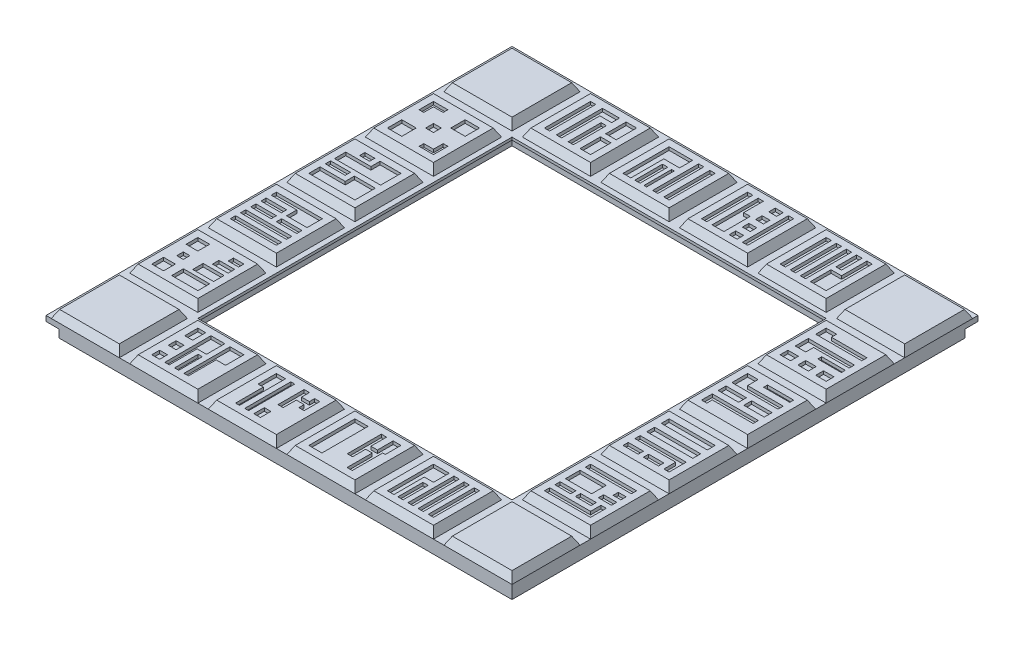
SolidWorks part; units mm, degrees
ref_plane "Front Plane" through (0, 0, 0) normal (0, 0, 1) x (1, 0, 0)
ref_plane "Top Plane" through (0, 0, 0) normal (0, 1, 0) x (1, 0, 0)
ref_plane "Right Plane" through (0, 0, 0) normal (1, 0, 0) x (0, 0, -1)
sketch "Sketch1" plane through (0, 0, 0) normal (0, 1, 0) x (1, 0, 0)
  line L1 (0, 0) -> (-180, 0)
  line L2 (0, 0) -> (0, 180)
  line L3 (0, 180) -> (-180, 180)
  line L4 (-180, 0) -> (-180, 180)
  dimension "D1" = 180
  dimension "D2" = 180
extrude "Boss-Extrude1" add sketch "Sketch1" along normal blind 5
sketch "Sketch2" plane through (0, 5, 0) normal (0, 1, 0) x (1, 0, 0)
  line L0 (-180, 180) -> (-180, 0) construction
  line L1 (-150, 150) -> (-30, 150)
  line L2 (-150, 150) -> (-150, 30)
  line L3 (-150, 30) -> (-30, 30)
  line L4 (-30, 150) -> (-30, 30)
  line L5 (0, 180) -> (-180, 180) construction
  dimension "D1" = 120
  dimension "D2" = 120
  dimension "D3" = 30
  dimension "D4" = 30
extrude "Cut-Extrude1" cut sketch "Sketch2" against normal through all
sketch "Sketch3" plane through (0, 5, 0) normal (0, 1, 0) x (1, 0, 0)
  line L0 (-180, 180) -> (-180, 0) construction
  line L1 (-178, 178) -> (-152, 178)
  line L2 (-178, 178) -> (-178, 152)
  line L3 (-178, 152) -> (-152, 152)
  line L4 (-152, 178) -> (-152, 152)
  line L5 (-148, 152) -> (-122, 152)
  line L6 (-148, 152) -> (-148, 178)
  line L7 (-148, 178) -> (-122, 178)
  line L8 (-122, 152) -> (-122, 178)
  line L9 (-118, 178) -> (-92, 178)
  line L10 (-118, 178) -> (-118, 152)
  line L11 (-118, 152) -> (-92, 152)
  line L12 (-92, 178) -> (-92, 152)
  line L13 (-88, 152) -> (-62, 152)
  line L14 (-88, 152) -> (-88, 178)
  line L15 (-88, 178) -> (-62, 178)
  line L16 (-62, 152) -> (-62, 178)
  line L17 (-58, 178) -> (-32, 178)
  line L18 (-58, 178) -> (-58, 152)
  line L19 (-58, 152) -> (-32, 152)
  line L20 (-32, 178) -> (-32, 152)
  line L21 (-28, 152) -> (-2, 152)
  line L22 (-28, 152) -> (-28, 178)
  line L23 (-28, 178) -> (-2, 178)
  line L24 (-2, 152) -> (-2, 178)
  line L25 (-28, 148) -> (-2, 148)
  line L26 (-28, 148) -> (-28, 122)
  line L27 (-28, 122) -> (-2, 122)
  line L28 (-2, 148) -> (-2, 122)
  line L29 (-2, 118) -> (-28, 118)
  line L30 (-2, 118) -> (-2, 92)
  line L31 (-2, 92) -> (-28, 92)
  line L32 (-28, 118) -> (-28, 92)
  line L33 (-28, 88) -> (-2, 88)
  line L34 (-28, 88) -> (-28, 62)
  line L35 (-28, 62) -> (-2, 62)
  line L36 (-2, 88) -> (-2, 62)
  line L37 (-28, 58) -> (-2, 58)
  line L38 (-28, 58) -> (-28, 32)
  line L39 (-28, 32) -> (-2, 32)
  line L40 (-2, 58) -> (-2, 32)
  line L41 (-28, 28) -> (-2, 28)
  line L42 (-28, 28) -> (-28, 2)
  line L43 (-28, 2) -> (-2, 2)
  line L44 (-2, 28) -> (-2, 2)
  line L45 (-32, 28) -> (-58, 28)
  line L46 (-32, 28) -> (-32, 2)
  line L47 (-32, 2) -> (-58, 2)
  line L48 (-58, 28) -> (-58, 2)
  line L49 (-62, 28) -> (-88, 28)
  line L50 (-62, 28) -> (-62, 2)
  line L51 (-62, 2) -> (-88, 2)
  line L52 (-88, 28) -> (-88, 2)
  line L53 (-92, 28) -> (-118, 28)
  line L54 (-92, 28) -> (-92, 2)
  line L55 (-92, 2) -> (-118, 2)
  line L56 (-118, 28) -> (-118, 2)
  line L57 (-122, 28) -> (-148, 28)
  line L58 (-122, 28) -> (-122, 2)
  line L59 (-122, 2) -> (-148, 2)
  line L60 (-148, 28) -> (-148, 2)
  line L61 (-152, 28) -> (-178, 28)
  line L62 (-152, 28) -> (-152, 2)
  line L63 (-152, 2) -> (-178, 2)
  line L64 (-178, 28) -> (-178, 2)
  line L65 (-178, 32) -> (-152, 32)
  line L66 (-178, 32) -> (-178, 58)
  line L67 (-178, 58) -> (-152, 58)
  line L68 (-152, 32) -> (-152, 58)
  line L69 (-178, 62) -> (-152, 62)
  line L70 (-178, 62) -> (-178, 88)
  line L71 (-178, 88) -> (-152, 88)
  line L72 (-152, 62) -> (-152, 88)
  line L73 (-178, 92) -> (-152, 92)
  line L74 (-178, 92) -> (-178, 118)
  line L75 (-178, 118) -> (-152, 118)
  line L76 (-152, 92) -> (-152, 118)
  line L77 (-178, 122) -> (-152, 122)
  line L78 (-178, 122) -> (-178, 148)
  line L79 (-178, 148) -> (-152, 148)
  line L80 (-152, 122) -> (-152, 148)
  line L81 (0, 180) -> (-180, 180) construction
  line L82 (-180, 0) -> (0, 0) construction
  line L83 (0, 0) -> (0, 180) construction
  dimension "D1" = 26
  dimension "D2" = 2
  dimension "D3" = 2
  dimension "D4" = 4
  dimension "D5" = 2
  dimension "D6" = 4
  dimension "D7" = 4
  dimension "D8" = 4
  dimension "D9" = 4
  dimension "D10" = 4
  dimension "D11" = 2
  dimension "D12" = 4
  dimension "D13" = 4
extrude "Boss-Extrude2" add sketch "Sketch3" along normal blind 3
chamfer "Chamfer1" distance 3 distance2 1.6 80 edges at (-15, 8, -178) (-2, 8, -165) (-15, 8, -152) (-28, 8, -165) (-105, 8, -2) (-118, 8, -15) (-105, 8, -28) (-92, 8, -15) (-135, 8, -2) (-148, 8, -15) (-135, 8, -28) (-122, 8, -15) (-165, 8, -2) (-178, 8, -15) (-165, 8, -28) (-152, 8, -15) (-165, 8, -58) (-152, 8, -45) (-165, 8, -32) (-178, 8, -45) (-165, 8, -88) (-152, 8, -75) (-165, 8, -62) (-178, 8, -75) (-165, 8, -118) (-152, 8, -105) (-165, 8, -92) (-178, 8, -105) (-15, 8, -58) (-2, 8, -45) (-15, 8, -32) (-28, 8, -45) (-75, 8, -2) (-88, 8, -15) (-75, 8, -28) (-62, 8, -15) (-45, 8, -2) (-58, 8, -15) (-45, 8, -28) (-32, 8, -15) (-15, 8, -28) (-2, 8, -15) (-15, 8, -2) (-28, 8, -15) (-15, 8, -88) (-2, 8, -75) (-15, 8, -62) (-28, 8, -75) (-15, 8, -92) (-28, 8, -105) (-15, 8, -118) (-2, 8, -105) (-15, 8, -148) (-2, 8, -135) (-15, 8, -122) (-28, 8, -135) (-75, 8, -178) (-62, 8, -165) (-75, 8, -152) (-88, 8, -165) (-105, 8, -178) (-92, 8, -165) (-105, 8, -152) (-118, 8, -165) (-135, 8, -178) (-122, 8, -165) (-135, 8, -152) (-148, 8, -165) (-165, 8, -148) (-152, 8, -135) (-165, 8, -122) (-178, 8, -135) (-165, 8, -178) (-152, 8, -165) (-165, 8, -152) (-178, 8, -165) (-45, 8, -178) (-32, 8, -165) (-45, 8, -152) (-58, 8, -165)
sketch "Sketch4" plane through (0, 8, 0) normal (0, 1, 0) x (1, 0, 0)
  line L0 (-123.6, 176.4) -> (-146.4, 176.4) construction
  line L1 (-143.8, 173.8) -> (-141.8, 173.8)
  line L2 (-143.8, 173.8) -> (-143.8, 156.2)
  line L3 (-143.8, 156.2) -> (-141.8, 156.2)
  line L4 (-141.8, 173.8) -> (-141.8, 156.2)
  line L5 (-139.25, 156.2) -> (-137.25, 156.2)
  line L6 (-139.25, 156.2) -> (-139.25, 173.8)
  line L7 (-139.25, 173.8) -> (-137.25, 173.8)
  line L8 (-137.25, 156.2) -> (-137.25, 173.8)
  line L9 (-137.25, 173.8) -> (-132.75, 173.8)
  line L10 (-146.4, 153.6) -> (-123.6, 153.6) construction
  line L11 (-137.25, 170.8) -> (-132.75, 170.8)
  line L12 (-132.75, 173.8) -> (-132.75, 170.8)
  line L13 (-132.75, 168.8) -> (-134.75, 168.8)
  line L14 (-132.75, 168.8) -> (-132.75, 156.2)
  line L15 (-132.75, 156.2) -> (-134.75, 156.2)
  line L16 (-134.75, 168.8) -> (-134.75, 156.2)
  line L17 (-130.2, 156.2) -> (-126.2, 156.2)
  line L18 (-130.2, 156.2) -> (-130.2, 164)
  line L19 (-130.2, 164) -> (-126.2, 164)
  line L20 (-126.2, 156.2) -> (-126.2, 164)
  line L21 (-130.2, 166) -> (-126.2, 166)
  line L22 (-130.2, 166) -> (-130.2, 173.8)
  line L23 (-130.2, 173.8) -> (-126.2, 173.8)
  line L24 (-126.2, 166) -> (-126.2, 173.8)
  line L25 (-113.8, 156.2) -> (-110.8, 156.2)
  line L26 (-113.8, 156.2) -> (-113.8, 173.8)
  line L27 (-113.8, 173.8) -> (-110.8, 173.8)
  line L28 (-110.8, 156.2) -> (-110.8, 173.8)
  line L29 (-110.8, 168.8) -> (-104.8, 168.8)
  line L30 (-146.4, 176.4) -> (-146.4, 153.6) construction
  line L31 (-110.8, 173.8) -> (-104.8, 173.8)
  line L32 (-104.8, 168.8) -> (-104.8, 173.8)
  line L33 (-109.3, 166.8) -> (-107.3, 166.8)
  line L34 (-109.3, 166.8) -> (-109.3, 156.2)
  line L35 (-109.3, 156.2) -> (-107.3, 156.2)
  line L36 (-107.3, 166.8) -> (-107.3, 156.2)
  line L37 (-105.8, 156.2) -> (-104.8, 156.2)
  line L38 (-105.8, 156.2) -> (-105.8, 166.8)
  line L39 (-105.8, 166.8) -> (-104.8, 166.8)
  line L40 (-104.8, 156.2) -> (-104.8, 166.8)
  line L41 (-102.5, 173.8) -> (-100.5, 173.8)
  line L42 (-102.5, 173.8) -> (-102.5, 156.2)
  line L43 (-102.5, 156.2) -> (-100.5, 156.2)
  line L44 (-100.5, 173.8) -> (-100.5, 156.2)
  line L45 (-98.2, 156.2) -> (-96.2, 156.2)
  line L46 (-98.2, 156.2) -> (-98.2, 173.8)
  line L47 (-98.2, 173.8) -> (-96.2, 173.8)
  line L48 (-96.2, 156.2) -> (-96.2, 173.8)
  line L49 (-83.8, 173.8) -> (-81.8, 173.8)
  line L50 (-83.8, 173.8) -> (-83.8, 156.2)
  line L51 (-83.8, 156.2) -> (-81.8, 156.2)
  line L52 (-81.8, 173.8) -> (-81.8, 156.2)
  line L53 (-79.7667, 156.2) -> (-77.7667, 156.2)
  line L54 (-79.7667, 156.2) -> (-79.7667, 173.8)
  line L55 (-79.7667, 173.8) -> (-77.7667, 173.8)
  line L56 (-77.7667, 156.2) -> (-77.7667, 173.8)
  line L57 (-77.7667, 166.2667) -> (-75.2667, 166.2667)
  line L58 (-123.6, 153.6) -> (-123.6, 176.4) construction
  line L59 (-77.7667, 156.2) -> (-75.2667, 156.2)
  line L60 (-75.2667, 166.2667) -> (-75.2667, 156.2)
  line L61 (-73.2333, 156.2) -> (-70.2333, 156.2)
  line L62 (-73.2333, 156.2) -> (-73.2333, 158.7)
  line L63 (-73.2333, 158.7) -> (-70.2333, 158.7)
  line L64 (-70.2333, 156.2) -> (-70.2333, 158.7)
  line L65 (-73.2333, 161.2333) -> (-70.2333, 161.2333)
  line L66 (-73.2333, 161.2333) -> (-73.2333, 163.7333)
  line L67 (-73.2333, 163.7333) -> (-70.2333, 163.7333)
  line L68 (-70.2333, 161.2333) -> (-70.2333, 163.7333)
  line L69 (-73.2333, 166.2667) -> (-70.2333, 166.2667)
  line L70 (-73.2333, 166.2667) -> (-73.2333, 168.7667)
  line L71 (-73.2333, 168.7667) -> (-70.2333, 168.7667)
  line L72 (-70.2333, 166.2667) -> (-70.2333, 168.7667)
  line L73 (-73.2333, 171.3) -> (-70.2333, 171.3)
  line L74 (-73.2333, 171.3) -> (-73.2333, 173.8)
  line L75 (-73.2333, 173.8) -> (-70.2333, 173.8)
  line L76 (-70.2333, 171.3) -> (-70.2333, 173.8)
  line L77 (-68.2, 173.8) -> (-66.2, 173.8)
  line L78 (-68.2, 173.8) -> (-68.2, 156.2)
  line L79 (-68.2, 156.2) -> (-66.2, 156.2)
  line L80 (-66.2, 173.8) -> (-66.2, 156.2)
  line L81 (-53.8, 173.8) -> (-51.8, 173.8)
  line L82 (-53.8, 173.8) -> (-53.8, 156.2)
  line L83 (-53.8, 156.2) -> (-51.8, 156.2)
  line L84 (-51.8, 173.8) -> (-51.8, 156.2)
  line L85 (-49.9333, 156.2) -> (-47.9333, 156.2)
  line L86 (-49.9333, 156.2) -> (-49.9333, 173.8)
  line L87 (-49.9333, 173.8) -> (-47.9333, 173.8)
  line L88 (-47.9333, 156.2) -> (-47.9333, 173.8)
  line L89 (-46.0667, 173.8) -> (-44.0667, 173.8)
  line L90 (-46.0667, 173.8) -> (-46.0667, 156.2)
  line L91 (-46.0667, 156.2) -> (-44.0667, 156.2)
  line L92 (-44.0667, 173.8) -> (-44.0667, 156.2)
  line L93 (-42.2, 173.8) -> (-40.0667, 173.8)
  line L94 (-42.2, 173.8) -> (-42.2, 165.9333)
  line L95 (-42.2, 165.9333) -> (-40.0667, 165.9333)
  line L96 (-40.0667, 173.8) -> (-40.0667, 165.9333)
  line L97 (-38.2, 173.8) -> (-36.2, 173.8)
  line L98 (-38.2, 173.8) -> (-38.2, 156.2)
  line L99 (-38.2, 156.2) -> (-36.2, 156.2)
  line L100 (-36.2, 173.8) -> (-36.2, 156.2)
  line L101 (-42.2, 156.2) -> (-38.2, 156.2)
  line L102 (-42.2, 156.2) -> (-42.2, 164.0667)
  line L103 (-42.2, 164.0667) -> (-38.2, 164.0667)
  line L104 (-93.6, 153.6) -> (-93.6, 176.4) construction
  line L105 (-116.4, 176.4) -> (-116.4, 153.6) construction
  line L106 (-63.6, 153.6) -> (-63.6, 176.4) construction
  line L107 (-86.4, 176.4) -> (-86.4, 153.6) construction
  line L108 (-56.4, 176.4) -> (-56.4, 153.6) construction
  line L109 (-33.6, 153.6) -> (-33.6, 176.4) construction
  line L110 (-70.2333, 171.3) -> (-70.2333, 168.7667) construction
  line L111 (-70.2333, 166.2667) -> (-70.2333, 163.7333) construction
  line L112 (-70.2333, 161.2333) -> (-70.2333, 158.7) construction
  line L113 (-141.8, 156.2) -> (-139.25, 156.2) construction
  line L114 (-132.75, 156.2) -> (-130.2, 156.2) construction
  line L115 (-104.8, 156.2) -> (-102.5, 156.2) construction
  line L116 (-100.5, 156.2) -> (-98.2, 156.2) construction
  line L117 (-51.8, 156.2) -> (-49.9333, 156.2) construction
  line L118 (-47.9333, 156.2) -> (-46.0667, 156.2) construction
  line L119 (-44.0667, 156.2) -> (-42.2, 156.2) construction
  line L120 (-42.2, 164.0667) -> (-42.2, 165.9333) construction
  line L121 (-40.0667, 173.8) -> (-38.2, 173.8) construction
  line L122 (-81.8, 156.2) -> (-79.7667, 156.2) construction
  line L123 (-75.2667, 156.2) -> (-73.2333, 156.2) construction
  line L124 (-70.2333, 156.2) -> (-68.2, 156.2) construction
  point P120 (-127.7927, 145.733)
  dimension "D1" = 2.6
  dimension "D2" = 2.6
  dimension "D3" = 2.6
  dimension "D4" = 2.6
  dimension "D5" = 2.6
  dimension "D6" = 2
  dimension "D7" = 2
  dimension "D8" = 2
  dimension "D9" = 1
  dimension "D10" = 2
  dimension "D11" = 2
  dimension "D12" = 2.6
  dimension "D13" = 2.6
  dimension "D14" = 2.6
  dimension "D15" = 2.6
  dimension "D16" = 2
  dimension "D17" = 2
  dimension "D18" = 2.5
  dimension "D19" = 2
  dimension "D21" = 3
  dimension "D23" = 2.6
  dimension "D24" = 2.6
  dimension "D25" = 2
  dimension "D26" = 2.5
  dimension "D27" = 2
  dimension "D28" = 3
  dimension "D29" = 2
  dimension "D30" = 2
  dimension "D31" = 4
  dimension "D32" = 4
  dimension "D33" = 3
  dimension "D34" = 6
  dimension "D35" = 1.5
  dimension "D36" = 5
  dimension "D37" = 2
  dimension "D38" = 2
  dimension "D39" = 2
  dimension "D40" = 2.5
  dimension "D41" = 2
  dimension "D42" = 2
  dimension "D43" = 4
extrude "Motifs_Ligne_1" cut sketch "Sketch4" against normal blind 1.2 contours L13 L16 L15 L14 | L12 L9 L8 L11 | L17 L20 L19 L18 | L21 L24 L23 L22 | L5 L8 L7 L6 | L25 L28 L27 L26 | L29 L32 L31 L28 | L36 L33 L34 L35 | L37 L40 L39 L38 | L44 L41 L42 L43 | L45 L48 L47 L46 | L103 L102 L101 L98 | L100 L97 L98 L99 | L96 L93 L94 L95 | L92 L89 L90 L91 | L85 L88 L87 L86 | L84 L81 L82 L83 | L73 L76 L75 L74 | L53 L56 L55 L54 | L60 L57 L56 L59 | L52 L49 L50 L51 | L65 L68 L67 L66 | L61 L64 L63 L62 | L69 L72 L71 L70 | L80 L77 L78 L79 | L2 L3 L4 L1
sketch "Sketch5" plane through (0, 0, 0) normal (0, -1, 0) x (1, 0, 0)
  line L0 (0, -175) -> (0, -180)
  line L1 (-180, -180) -> (-180, 0)
  line L2 (-180, 0) -> (-175, 0)
  line L4 (-175, -175) -> (0, -175)
  line L5 (0, -180) -> (-180, -180)
  line L6 (-175, 0) -> (-175, -175)
  line L7 (-180, 0) -> (0, 0) construction
  dimension "D1" = 5
  dimension "D2" = 5
  dimension "D3" = 0
  dimension "D4" = 0
extrude "Cut-Extrude3" cut sketch "Sketch5" against normal blind 3
sketch "Sketch6" plane through (0, 0, 0) normal (0, -1, 0) x (1, 0, 0)
  line L0 (0, 0) -> (0, -194.7494)
  line L1 (0, -194.7494) -> (-2, -194.7494)
  line L2 (-2, -194.7494) -> (-2, -2)
  line L3 (-2, -2) -> (-190.0347, -2)
  line L4 (-190.0347, -2) -> (-190.0347, 0)
  line L5 (-190.0347, 0) -> (0, 0)
  dimension "D1" = 2
  dimension "D2" = 2
extrude "Cut-Extrude4" cut sketch "Sketch6" against normal through all
sketch "Sketch7" plane through (0, 8, 0) normal (0, 1, 0) x (1, 0, 0)
  line L0 (-173.8, 146.4) -> (-173.8, 33.6) construction
  line L1 (-153.6, 146.4) -> (-176.4, 146.4) construction
  line L2 (-176.4, 33.6) -> (-153.6, 33.6) construction
  line L3 (-156.2, 146.4) -> (-156.2, 33.6) construction
  line L4 (-176.4, 36.2) -> (-153.6, 36.2) construction
  line L5 (-176.4, 56.4) -> (-176.4, 33.6) construction
  line L6 (-153.6, 33.6) -> (-153.6, 56.4) construction
  line L7 (-176.4, 143.8) -> (-153.6, 143.8) construction
  line L8 (-176.4, 146.4) -> (-176.4, 123.6) construction
  line L9 (-153.6, 123.6) -> (-153.6, 146.4) construction
  line L10 (-176.4, 126.2) -> (-153.6, 126.2) construction
  line L11 (-176.4, 96.2) -> (-153.6, 96.2) construction
  line L12 (-176.4, 116.4) -> (-176.4, 93.6) construction
  line L13 (-153.6, 93.6) -> (-153.6, 116.4) construction
  line L14 (-176.4, 113.8) -> (-153.6, 113.8) construction
  line L15 (-176.4, 83.8) -> (-153.6, 83.8) construction
  line L16 (-176.4, 86.4) -> (-176.4, 63.6) construction
  line L17 (-153.6, 63.6) -> (-153.6, 86.4) construction
  line L18 (-153.6, 66.2) -> (-176.4, 66.2) construction
  line L19 (-176.4, 53.8) -> (-153.6, 53.8) construction
  line L20 (-176.4, 123.6) -> (-153.6, 123.6) construction
  line L21 (-153.6, 116.4) -> (-176.4, 116.4) construction
  line L22 (-176.4, 93.6) -> (-153.6, 93.6) construction
  line L23 (-153.6, 86.4) -> (-176.4, 86.4) construction
  line L24 (-176.4, 63.6) -> (-153.6, 63.6) construction
  line L25 (-153.6, 56.4) -> (-176.4, 56.4) construction
  line L26 (-173.8, 138.3) -> (-172, 138.3)
  line L27 (-173.8, 126.2) -> (-168.3, 126.2)
  line L28 (-173.8, 126.2) -> (-173.8, 131.7)
  line L29 (-173.8, 131.7) -> (-168.3, 131.7)
  line L30 (-168.3, 126.2) -> (-168.3, 131.7)
  line L31 (-166.5, 133.5) -> (-163.5, 133.5)
  line L32 (-166.5, 133.5) -> (-166.5, 136.5)
  line L33 (-166.5, 136.5) -> (-163.5, 136.5)
  line L34 (-163.5, 133.5) -> (-163.5, 136.5)
  line L35 (-156.2, 143.8) -> (-161.7, 143.8)
  line L36 (-156.2, 143.8) -> (-156.2, 138.3)
  line L37 (-156.2, 138.3) -> (-161.7, 138.3)
  line L38 (-161.7, 143.8) -> (-161.7, 138.3)
  line L39 (-172, 138.3) -> (-172, 142)
  line L40 (-172, 142) -> (-168.3, 142)
  line L41 (-168.3, 142) -> (-168.3, 143.8)
  line L42 (-168.3, 143.8) -> (-173.8, 143.8)
  line L43 (-173.8, 143.8) -> (-173.8, 138.3)
  line L44 (-161.7, 126.2) -> (-156.2, 126.2)
  line L45 (-156.2, 126.2) -> (-156.2, 131.7)
  line L46 (-156.2, 131.7) -> (-158, 131.7)
  line L47 (-158, 131.7) -> (-158, 128)
  line L48 (-158, 128) -> (-161.7, 128)
  line L49 (-161.7, 126.2) -> (-161.7, 128)
  line L50 (-173.8, 131.7) -> (-173.8, 138.3) construction
  line L51 (-168.3, 143.8) -> (-161.7, 143.8) construction
  line L52 (-168.3, 126.2) -> (-161.7, 126.2) construction
  line L53 (-156.2, 131.7) -> (-156.2, 138.3) construction
  line L54 (-172, 138.3) -> (-172, 131.7) construction
  line L55 (-166.5, 133.5) -> (-173.8, 133.5) construction
  line L56 (-166.5, 133.5) -> (-166.5, 126.2) construction
  line L57 (-163.5, 136.5) -> (-163.5, 143.8) construction
  line L58 (-163.5, 136.5) -> (-156.2, 136.5) construction
  line L59 (-173.8, 106) -> (-156.2, 106)
  line L60 (-156.2, 106) -> (-156.2, 113.8)
  line L61 (-156.2, 113.8) -> (-164.2, 113.8)
  line L62 (-164.2, 113.8) -> (-164.2, 110.3)
  line L63 (-164.2, 110.3) -> (-173.8, 110.3)
  line L64 (-173.8, 110.3) -> (-173.8, 106)
  line L65 (-173.8, 96.2) -> (-173.8, 100.5)
  line L66 (-173.8, 100.5) -> (-164.2, 100.5)
  line L67 (-164.2, 100.5) -> (-164.2, 104)
  line L68 (-164.2, 104) -> (-156.2, 104)
  line L69 (-156.2, 104) -> (-156.2, 96.2)
  line L70 (-156.2, 96.2) -> (-173.8, 96.2)
  line L71 (-173.8, 83.8) -> (-156.2, 83.8)
  line L72 (-173.8, 104.5) -> (-166.2, 104.5)
  line L73 (-173.8, 104.5) -> (-173.8, 102.5)
  line L74 (-173.8, 102.5) -> (-166.2, 102.5)
  line L75 (-166.2, 104.5) -> (-166.2, 102.5)
  line L76 (-170, 113.8) -> (-166.2, 113.8)
  line L77 (-170, 113.8) -> (-170, 111.8)
  line L78 (-170, 111.8) -> (-166.2, 111.8)
  line L79 (-166.2, 113.8) -> (-166.2, 111.8)
  line L80 (-173.8, 66.2) -> (-156.2, 66.2)
  line L81 (-173.8, 66.2) -> (-173.8, 68.2)
  line L82 (-173.8, 68.2) -> (-156.2, 68.2)
  line L83 (-156.2, 66.2) -> (-156.2, 68.2)
  line L84 (-156.2, 70.1) -> (-173.8, 70.1)
  line L85 (-156.2, 70.1) -> (-156.2, 72.1)
  line L86 (-156.2, 72.1) -> (-173.8, 72.1)
  line L87 (-173.8, 70.1) -> (-173.8, 72.1)
  line L88 (-173.8, 74) -> (-166, 74)
  line L89 (-173.8, 74) -> (-173.8, 76)
  line L90 (-173.8, 76) -> (-166, 76)
  line L91 (-166, 74) -> (-166, 76)
  line L92 (-164, 76) -> (-156.2, 76)
  line L93 (-164, 76) -> (-164, 74)
  line L94 (-164, 74) -> (-156.2, 74)
  line L95 (-156.2, 76) -> (-156.2, 74)
  line L96 (-173.8, 77.9) -> (-166, 77.9)
  line L97 (-173.8, 77.9) -> (-173.8, 79.9)
  line L98 (-173.8, 79.9) -> (-166, 79.9)
  line L99 (-166, 77.9) -> (-166, 79.9)
  line L100 (-156.2, 83.8) -> (-156.2, 77.9)
  line L101 (-156.2, 77.9) -> (-164, 77.9)
  line L102 (-164, 77.9) -> (-164, 81.8)
  line L103 (-164, 81.8) -> (-173.8, 81.8)
  line L104 (-173.8, 81.8) -> (-173.8, 83.8)
  line L105 (-173.8, 68.2) -> (-173.8, 70.1) construction
  line L106 (-173.8, 72.1) -> (-173.8, 74) construction
  line L107 (-166, 79.9) -> (-166, 81.8) construction
  line L108 (-166, 77.9) -> (-166, 76) construction
  line L109 (-166, 74) -> (-166, 72.1) construction
  line L110 (-166, 70.1) -> (-166, 68.2) construction
  line L111 (-159.5704, 40.7) -> (-159.5704, 42.2333) construction
  line L112 (-173.8, 53.8) -> (-169.3, 53.8)
  line L113 (-173.8, 53.8) -> (-173.8, 49.3)
  line L114 (-173.8, 49.3) -> (-169.3, 49.3)
  line L115 (-169.3, 53.8) -> (-169.3, 49.3)
  line L116 (-173.8, 36.2) -> (-169.3, 36.2)
  line L117 (-173.8, 36.2) -> (-173.8, 40.7)
  line L118 (-173.8, 40.7) -> (-169.3, 40.7)
  line L119 (-169.3, 36.2) -> (-169.3, 40.7)
  line L120 (-169.3, 43.75) -> (-171.8, 43.75)
  line L121 (-169.3, 43.75) -> (-169.3, 46.25)
  line L122 (-169.3, 46.25) -> (-171.8, 46.25)
  line L123 (-171.8, 43.75) -> (-171.8, 46.25)
  line L124 (-156.2, 53.8) -> (-160.2, 53.8)
  line L125 (-156.2, 53.8) -> (-156.2, 51.8)
  line L126 (-156.2, 51.8) -> (-160.2, 51.8)
  line L127 (-160.2, 53.8) -> (-160.2, 51.8)
  line L128 (-156.2, 50.2667) -> (-162.2, 50.2667)
  line L129 (-156.2, 50.2667) -> (-156.2, 47.7667)
  line L130 (-156.2, 47.7667) -> (-162.2, 47.7667)
  line L131 (-162.2, 50.2667) -> (-162.2, 47.7667)
  line L132 (-156.2, 46.2333) -> (-164.2, 46.2333)
  line L133 (-156.2, 46.2333) -> (-156.2, 42.2333)
  line L134 (-156.2, 42.2333) -> (-164.2, 42.2333)
  line L135 (-164.2, 46.2333) -> (-164.2, 42.2333)
  line L136 (-156.2, 40.7) -> (-166.2, 40.7)
  line L137 (-156.2, 40.7) -> (-156.2, 36.2)
  line L138 (-156.2, 36.2) -> (-166.2, 36.2)
  line L139 (-166.2, 40.7) -> (-166.2, 36.2)
  line L140 (-159.5704, 46.2333) -> (-159.5704, 47.7667) construction
  line L141 (-159.5704, 50.2667) -> (-159.5704, 51.8) construction
  line L142 (-169.3, 46.25) -> (-169.3, 49.3) construction
  line L143 (-169.3, 43.75) -> (-169.3, 40.7) construction
  dimension "D1" = 2.6
  dimension "D2" = 2.6
  dimension "D3" = 2.6
  dimension "D4" = 2.6
  dimension "D5" = 2.6
  dimension "D6" = 2.6
  dimension "D7" = 2.6
  dimension "D8" = 2.6
  dimension "D9" = 2.6
  dimension "D10" = 2.6
  dimension "D11" = 1.8
  dimension "D12" = 5.5
  dimension "D13" = 1.5
  dimension "D14" = 3
  dimension "D15" = 2
  dimension "D16" = 2
  dimension "D17" = 2
  dimension "D18" = 8
  dimension "D19" = 2
  dimension "D20" = 3.8
  dimension "D21" = 2
  dimension "D22" = 2
  dimension "D23" = 2
  dimension "D24" = 2.5
  dimension "D25" = 4
  dimension "D26" = 4.5
  dimension "D27" = 10
  dimension "D28" = 8
  dimension "D29" = 6
  dimension "D30" = 4
  dimension "D31" = 2.5
  dimension "D32" = 4.5
extrude "Cut-Extrude5" cut sketch "Sketch7" against normal blind 1.2
sketch "Sketch8" plane through (0, 8, 0) normal (0, 1, 0) x (1, 0, 0)
  line L0 (-23.8, 38.2) -> (-23.8, 36.2)
  line L1 (-15.2, 133.5) -> (-6.2, 133.5)
  line L2 (-15.2, 133.5) -> (-15.2, 132)
  line L3 (-15.2, 132) -> (-6.2, 132)
  line L4 (-6.2, 133.5) -> (-6.2, 132)
  line L5 (-23.8, 129.2) -> (-19.8, 129.2)
  line L6 (-23.8, 129.2) -> (-23.8, 126.2)
  line L7 (-23.8, 126.2) -> (-19.8, 126.2)
  line L8 (-19.8, 129.2) -> (-19.8, 126.2)
  line L9 (-17, 129.2) -> (-13, 129.2)
  line L10 (-17, 129.2) -> (-17, 126.2)
  line L11 (-17, 126.2) -> (-13, 126.2)
  line L12 (-13, 129.2) -> (-13, 126.2)
  line L13 (-10.2, 129.2) -> (-6.2, 129.2)
  line L14 (-10.2, 129.2) -> (-10.2, 126.2)
  line L15 (-10.2, 126.2) -> (-6.2, 126.2)
  line L16 (-6.2, 129.2) -> (-6.2, 126.2)
  line L17 (-16.2, 113.8) -> (-6.2, 113.8)
  line L18 (-16.2, 113.8) -> (-16.2, 112.3)
  line L19 (-16.2, 112.3) -> (-6.2, 112.3)
  line L20 (-6.2, 113.8) -> (-6.2, 112.3)
  line L21 (-23.8, 105.5524) -> (-16, 105.5524)
  line L22 (-23.8, 105.5524) -> (-23.8, 102.5524)
  line L23 (-23.8, 102.5524) -> (-16, 102.5524)
  line L24 (-16, 105.5524) -> (-16, 102.5524)
  line L25 (-14, 105.5524) -> (-6.2, 105.5524)
  line L26 (-14, 105.5524) -> (-14, 102.5524)
  line L27 (-14, 102.5524) -> (-6.2, 102.5524)
  line L28 (-6.2, 105.5524) -> (-6.2, 102.5524)
  line L29 (-23.8, 83.8) -> (-6.2, 83.8)
  line L30 (-23.8, 83.8) -> (-23.8, 80.8)
  line L31 (-23.8, 80.8) -> (-6.2, 80.8)
  line L32 (-6.2, 83.8) -> (-6.2, 80.8)
  line L33 (-6.2, 78.2667) -> (-23.8, 78.2667)
  line L34 (-6.2, 78.2667) -> (-6.2, 75.2667)
  line L35 (-6.2, 75.2667) -> (-23.8, 75.2667)
  line L36 (-23.8, 78.2667) -> (-23.8, 75.2667)
  line L37 (-23.8, 68.2) -> (-18, 68.2)
  line L38 (-23.8, 68.2) -> (-23.8, 66.2)
  line L39 (-23.8, 66.2) -> (-18, 66.2)
  line L40 (-18, 68.2) -> (-18, 66.2)
  line L41 (-16, 68.2) -> (-10.2, 68.2)
  line L42 (-16, 68.2) -> (-16, 66.2)
  line L43 (-16, 66.2) -> (-10.2, 66.2)
  line L44 (-10.2, 68.2) -> (-10.2, 66.2)
  line L45 (-23.8, 53.8) -> (-6.2, 53.8)
  line L46 (-23.8, 53.8) -> (-23.8, 51.8)
  line L47 (-23.8, 51.8) -> (-6.2, 51.8)
  line L48 (-6.2, 53.8) -> (-6.2, 51.8)
  line L49 (-23.8, 49.8) -> (-13.8, 49.8)
  line L50 (-23.8, 49.8) -> (-23.8, 44.2)
  line L51 (-23.8, 44.2) -> (-13.8, 44.2)
  line L52 (-13.8, 49.8) -> (-13.8, 44.2)
  line L53 (-9.2, 49.8) -> (-6.2, 49.8)
  line L54 (-9.2, 49.8) -> (-9.2, 47.8)
  line L55 (-9.2, 47.8) -> (-6.2, 47.8)
  line L56 (-6.2, 49.8) -> (-6.2, 47.8)
  line L57 (-11.2, 46.2) -> (-6.2, 46.2)
  line L58 (-11.2, 46.2) -> (-11.2, 44.2)
  line L59 (-11.2, 44.2) -> (-6.2, 44.2)
  line L60 (-6.2, 46.2) -> (-6.2, 44.2)
  line L61 (-23.8, 42.2) -> (-17.8, 42.2)
  line L62 (-23.8, 42.2) -> (-23.8, 40.2)
  line L63 (-23.8, 40.2) -> (-17.8, 40.2)
  line L64 (-17.8, 42.2) -> (-17.8, 40.2)
  line L65 (-16, 42.2) -> (-10, 42.2)
  line L66 (-16, 42.2) -> (-16, 40.2)
  line L67 (-16, 40.2) -> (-10, 40.2)
  line L68 (-10, 42.2) -> (-10, 40.2)
  line L69 (-23.8, 36.2) -> (-6.2, 36.2)
  line L70 (-6.2, 36.2) -> (-6.2, 42.2)
  line L71 (-6.2, 42.2) -> (-8.2, 42.2)
  line L72 (-8.2, 42.2) -> (-8.2, 38.2)
  line L73 (-8.2, 38.2) -> (-23.8, 38.2)
  line L74 (-23.8, 70.7333) -> (-23.8, 72.7333)
  line L75 (-23.8, 72.7333) -> (-6.2, 72.7333)
  line L76 (-6.2, 72.7333) -> (-6.2, 66.2)
  line L77 (-6.2, 66.2) -> (-8.2, 66.2)
  line L78 (-8.2, 66.2) -> (-8.2, 70.7333)
  line L79 (-8.2, 70.7333) -> (-23.8, 70.7333)
  line L80 (-23.8, 96.2) -> (-23.8, 100.3049)
  line L81 (-23.8, 100.3049) -> (-6.2, 100.3049)
  line L82 (-6.2, 100.3049) -> (-6.2, 98.3049)
  line L83 (-6.2, 98.3049) -> (-21.8, 98.3049)
  line L84 (-21.8, 98.3049) -> (-21.8, 96.2)
  line L85 (-21.8, 96.2) -> (-23.8, 96.2)
  line L86 (-23.8, 113.8) -> (-23.8, 107.8)
  line L87 (-23.8, 107.8) -> (-6.2, 107.8)
  line L88 (-6.2, 107.8) -> (-6.2, 109.8)
  line L89 (-6.2, 109.8) -> (-19.8, 109.8)
  line L90 (-19.8, 109.8) -> (-19.8, 113.8)
  line L91 (-19.8, 113.8) -> (-23.8, 113.8)
  line L92 (-23.8, 132) -> (-19.8, 132)
  line L93 (-19.8, 132) -> (-19.8, 135)
  line L94 (-19.8, 135) -> (-6.2, 135)
  line L95 (-6.2, 135) -> (-6.2, 137)
  line L96 (-6.2, 137) -> (-23.8, 137)
  line L97 (-23.8, 137) -> (-23.8, 132)
  line L98 (-23.8, 143.8) -> (-23.8, 139.8)
  line L99 (-23.8, 139.8) -> (-6.2, 139.8)
  line L100 (-6.2, 139.8) -> (-6.2, 141.8)
  line L101 (-6.2, 141.8) -> (-19.8, 141.8)
  line L102 (-19.8, 141.8) -> (-19.8, 143.8)
  line L103 (-19.8, 143.8) -> (-23.8, 143.8)
  line L104 (-3.6, 33.6) -> (-3.6, 56.4) construction
  line L105 (-26.4, 146.4) -> (-26.4, 123.6) construction
  line L106 (-3.6, 146.4) -> (-26.4, 146.4) construction
  line L107 (-26.4, 123.6) -> (-3.6, 123.6) construction
  line L108 (-3.6, 116.4) -> (-26.4, 116.4) construction
  line L109 (-26.4, 93.6) -> (-3.6, 93.6) construction
  line L110 (-3.6, 86.4) -> (-26.4, 86.4) construction
  line L111 (-26.4, 63.6) -> (-3.6, 63.6) construction
  line L112 (-3.6, 56.4) -> (-26.4, 56.4) construction
  line L113 (-26.4, 33.6) -> (-3.6, 33.6) construction
  line L114 (-23.8, 68.2) -> (-23.8, 70.7333) construction
  line L115 (-23.8, 72.7333) -> (-23.8, 75.2667) construction
  line L116 (-23.8, 78.2667) -> (-23.8, 80.8) construction
  line L117 (-23.8, 38.2) -> (-23.8, 40.2) construction
  line L118 (-23.8, 42.2) -> (-23.8, 44.2) construction
  line L119 (-23.8, 49.8) -> (-23.8, 51.8) construction
  line L120 (-17.8, 42.2) -> (-16, 42.2) construction
  line L121 (-10, 42.2) -> (-8.2, 42.2) construction
  line L122 (-23.8, 100.3049) -> (-23.8, 102.5524) construction
  line L123 (-23.8, 105.5524) -> (-23.8, 107.8) construction
  line L124 (-23.8, 129.2) -> (-23.8, 132) construction
  line L125 (-23.8, 137) -> (-23.8, 139.8) construction
  line L126 (-19.8, 126.2) -> (-17, 126.2) construction
  line L127 (-13, 126.2) -> (-10.2, 126.2) construction
  dimension "D1" = 2.6
  dimension "D2" = 2.6
  dimension "D3" = 2.6
  dimension "D4" = 2.6
  dimension "D5" = 2.6
  dimension "D6" = 2.6
  dimension "D7" = 2.6
  dimension "D8" = 2.6
  dimension "D9" = 2.6
  dimension "D10" = 2.6
  dimension "D11" = 3
  dimension "D12" = 2
  dimension "D13" = 2
  dimension "D14" = 2
  dimension "D15" = 2
  dimension "D16" = 2
  dimension "D17" = 2
  dimension "D18" = 2
  dimension "D19" = 2
  dimension "D20" = 2
  dimension "D21" = 10
  dimension "D22" = 6
  dimension "D23" = 2
  dimension "D24" = 5
  dimension "D25" = 3
  dimension "D26" = 2
  dimension "D27" = 2
  dimension "D28" = 2
  dimension "D29" = 1.5
  dimension "D30" = 2
  dimension "D31" = 3
  dimension "D32" = 10
  dimension "D33" = 4
  dimension "D34" = 4.1049
  dimension "D35" = 6
  dimension "D36" = 2
  dimension "D37" = 4
  dimension "D38" = 4
  dimension "D39" = 4
  dimension "D40" = 5
  dimension "D41" = 2
  dimension "D42" = 3
  dimension "D43" = 4
  dimension "D44" = 9
  dimension "D45" = 1.5
extrude "Cut-Extrude6" cut sketch "Sketch8" against normal blind 1.2
sketch "Sketch9" plane through (0, 8, 0) normal (0, 1, 0) x (1, 0, 0)
  line L0 (-138.8, 6.2) -> (-138.8, 23.8)
  line L1 (-143.8, 23.8) -> (-140.8, 23.8)
  line L2 (-143.8, 23.8) -> (-143.8, 18.8)
  line L3 (-143.8, 18.8) -> (-140.8, 18.8)
  line L4 (-140.8, 23.8) -> (-140.8, 18.8)
  line L5 (-143.8, 15.5) -> (-140.8, 15.5)
  line L6 (-143.8, 15.5) -> (-143.8, 12.5)
  line L7 (-143.8, 12.5) -> (-140.8, 12.5)
  line L8 (-140.8, 15.5) -> (-140.8, 12.5)
  line L9 (-143.8, 9.2) -> (-140.8, 9.2)
  line L10 (-143.8, 9.2) -> (-143.8, 6.2)
  line L11 (-143.8, 6.2) -> (-140.8, 6.2)
  line L12 (-140.8, 9.2) -> (-140.8, 6.2)
  line L13 (-135.1, 15.2) -> (-133.5, 15.2)
  line L14 (-135.1, 15.2) -> (-135.1, 6.2)
  line L15 (-135.1, 6.2) -> (-133.5, 6.2)
  line L16 (-133.5, 15.2) -> (-133.5, 6.2)
  line L17 (-138.8, 23.8) -> (-133.5, 23.8)
  line L18 (-133.5, 23.8) -> (-133.5, 16.8)
  line L19 (-133.5, 16.8) -> (-137.1, 16.8)
  line L20 (-137.1, 16.8) -> (-137.1, 6.2)
  line L21 (-137.1, 6.2) -> (-138.8, 6.2)
  line L22 (-131.5, 6.2) -> (-131.5, 23.8)
  line L23 (-131.5, 23.8) -> (-126.2, 23.8)
  line L24 (-126.2, 23.8) -> (-126.2, 16.8)
  line L25 (-126.2, 16.8) -> (-129.8, 16.8)
  line L26 (-129.8, 16.8) -> (-129.8, 6.2)
  line L27 (-129.8, 6.2) -> (-131.5, 6.2)
  line L28 (-111.8, 16.8) -> (-113.8, 16.8)
  line L29 (-113.8, 16.8) -> (-113.8, 23.8)
  line L30 (-113.8, 23.8) -> (-110.3, 23.8)
  line L31 (-110.3, 23.8) -> (-110.3, 6.2)
  line L32 (-110.3, 6.2) -> (-111.8, 6.2)
  line L33 (-111.8, 6.2) -> (-111.8, 16.8)
  line L34 (-108.3, 6.2) -> (-108.3, 23.8)
  line L35 (-108.3, 23.8) -> (-106.8, 23.8)
  line L36 (-106.8, 23.8) -> (-106.8, 6.2)
  line L37 (-106.8, 6.2) -> (-108.3, 6.2)
  line L38 (-104.8, 6.2) -> (-104.8, 10.2)
  line L39 (-104.8, 10.2) -> (-102.3, 10.2)
  line L40 (-102.3, 10.2) -> (-102.3, 6.2)
  line L41 (-102.3, 6.2) -> (-104.8, 6.2)
  line L42 (-103.2, 13.8) -> (-103.2, 23.8)
  line L43 (-103.2, 23.8) -> (-101.2, 23.8)
  line L44 (-101.2, 23.8) -> (-101.2, 20.8)
  line L45 (-101.2, 20.8) -> (-98.2, 20.8)
  line L46 (-98.2, 20.8) -> (-98.2, 22.8)
  line L47 (-98.2, 22.8) -> (-96.2, 22.8)
  line L48 (-96.2, 22.8) -> (-96.2, 16.8)
  line L49 (-96.2, 16.8) -> (-98.2, 16.8)
  line L50 (-98.2, 16.8) -> (-98.2, 18.8)
  line L51 (-98.2, 18.8) -> (-101.2, 18.8)
  line L52 (-101.2, 18.8) -> (-101.2, 13.8)
  line L53 (-101.2, 13.8) -> (-103.2, 13.8)
  line L54 (-83.8, 23.8) -> (-78.8, 23.8)
  line L55 (-78.8, 23.8) -> (-78.8, 6.2)
  line L56 (-78.8, 6.2) -> (-83.8, 6.2)
  line L57 (-83.8, 6.2) -> (-83.8, 23.8)
  line L58 (-73.7, 10.8) -> (-73.7, 23.8)
  line L59 (-73.7, 23.8) -> (-71.7, 23.8)
  line L60 (-71.7, 23.8) -> (-71.7, 17.8)
  line L61 (-71.7, 17.8) -> (-69.2, 17.8)
  line L62 (-69.2, 17.8) -> (-69.2, 23.8)
  line L63 (-69.2, 23.8) -> (-66.2, 23.8)
  line L64 (-66.2, 23.8) -> (-66.2, 17.8)
  line L65 (-66.2, 17.8) -> (-67.2, 17.8)
  line L66 (-67.2, 17.8) -> (-67.2, 6.2)
  line L67 (-67.2, 6.2) -> (-69.2, 6.2)
  line L68 (-69.2, 6.2) -> (-69.2, 15.8)
  line L69 (-69.2, 15.8) -> (-71.7, 15.8)
  line L70 (-71.7, 15.8) -> (-71.7, 10.8)
  line L71 (-71.7, 10.8) -> (-73.7, 10.8)
  line L72 (-53.8, 6.2) -> (-53.8, 23.8)
  line L73 (-53.8, 23.8) -> (-47.8, 23.8)
  line L74 (-47.8, 23.8) -> (-47.8, 17.8)
  line L75 (-47.8, 17.8) -> (-51.3, 17.8)
  line L76 (-51.3, 17.8) -> (-51.3, 6.2)
  line L77 (-51.3, 6.2) -> (-53.8, 6.2)
  line L78 (-63.6, 26.4) -> (-86.4, 26.4) construction
  line L79 (-47.8, 15.8) -> (-49.8, 15.8)
  line L80 (-47.8, 15.8) -> (-47.8, 6.2)
  line L81 (-47.8, 6.2) -> (-49.8, 6.2)
  line L82 (-49.8, 15.8) -> (-49.8, 6.2)
  line L83 (-45.9333, 6.2) -> (-43.9333, 6.2)
  line L84 (-45.9333, 6.2) -> (-45.9333, 23.8)
  line L85 (-45.9333, 23.8) -> (-43.9333, 23.8)
  line L86 (-43.9333, 6.2) -> (-43.9333, 23.8)
  line L87 (-42.0667, 23.8) -> (-40.0667, 23.8)
  line L88 (-42.0667, 23.8) -> (-42.0667, 6.2)
  line L89 (-42.0667, 6.2) -> (-40.0667, 6.2)
  line L90 (-40.0667, 23.8) -> (-40.0667, 6.2)
  line L91 (-38.2, 6.2) -> (-36.2, 6.2)
  line L92 (-38.2, 6.2) -> (-38.2, 23.8)
  line L93 (-38.2, 23.8) -> (-36.2, 23.8)
  line L94 (-36.2, 6.2) -> (-36.2, 23.8)
  line L95 (-146.4, 3.6) -> (-123.6, 3.6) construction
  line L96 (-146.4, 26.4) -> (-146.4, 3.6) construction
  line L97 (-123.6, 3.6) -> (-123.6, 26.4) construction
  line L98 (-116.4, 26.4) -> (-116.4, 3.6) construction
  line L99 (-93.6, 3.6) -> (-93.6, 26.4) construction
  line L100 (-86.4, 26.4) -> (-86.4, 3.6) construction
  line L101 (-63.6, 3.6) -> (-63.6, 26.4) construction
  line L102 (-56.4, 26.4) -> (-56.4, 3.6) construction
  line L103 (-33.6, 3.6) -> (-33.6, 26.4) construction
  line L104 (-47.8, 6.2) -> (-45.9333, 6.2) construction
  line L105 (-43.9333, 6.2) -> (-42.0667, 6.2) construction
  line L106 (-40.0667, 6.2) -> (-38.2, 6.2) construction
  line L107 (-143.8, 9.2) -> (-143.8, 12.5) construction
  line L108 (-143.8, 15.5) -> (-143.8, 18.8) construction
  line L109 (-140.8, 6.2) -> (-138.8, 6.2) construction
  line L110 (-133.5, 6.2) -> (-131.5, 6.2) construction
  line L111 (-137.1, 6.2) -> (-135.1, 6.2) construction
  dimension "D1" = 2.6
  dimension "D2" = 2.6
  dimension "D3" = 2.6
  dimension "D4" = 2.6
  dimension "D5" = 2.6
  dimension "D6" = 2.6
  dimension "D7" = 2.6
  dimension "D8" = 2.6
  dimension "D9" = 2.6
  dimension "D10" = 2.6
  dimension "D11" = 2
  dimension "D12" = 6
  dimension "D13" = 2.5
  dimension "D14" = 2
  dimension "D15" = 6
  dimension "D16" = 2
  dimension "D17" = 5
  dimension "D18" = 2
  dimension "D19" = 2
  dimension "D20" = 3
  dimension "D21" = 2.5
  dimension "D22" = 2.5
  dimension "D23" = 13
  dimension "D24" = 6
  dimension "D25" = 5
  dimension "D26" = 1.5
  dimension "D27" = 1.5
  dimension "D28" = 2
  dimension "D29" = 2.5
  dimension "D30" = 4
  dimension "D31" = 2
  dimension "D32" = 2
  dimension "D33" = 10
  dimension "D34" = 2
  dimension "D35" = 3
  dimension "D36" = 2
  dimension "D37" = 2
  dimension "D38" = 2
  dimension "D39" = 2
  dimension "D40" = 2
  dimension "D41" = 3
  dimension "D42" = 7
  dimension "D43" = 3
  dimension "D44" = 5
  dimension "D45" = 3
  dimension "D46" = 3
  dimension "D47" = 2
  dimension "D48" = 9
  dimension "D49" = 1.6
extrude "Cut-Extrude7" cut sketch "Sketch9" against normal blind 1.2
sketch "Sketch10" plane through (0, 0, 0) normal (0, -1, 0) x (1, 0, 0)
  line L1 (-30, -150) -> (-150, -150)
  line L2 (-30, -150) -> (-30, -30)
  line L3 (-30, -30) -> (-150, -30)
  line L4 (-150, -150) -> (-150, -30)
  line L5 (-27.9, -152.1) -> (-152.1, -152.1)
  line L6 (-27.9, -152.1) -> (-27.9, -27.9)
  line L7 (-27.9, -27.9) -> (-152.1, -27.9)
  line L8 (-152.1, -152.1) -> (-152.1, -27.9)
  dimension "D1" = 2.1
  dimension "D2" = 2.1
  dimension "D3" = 2.1
  dimension "D4" = 2.1
extrude "Cut-Extrude8" cut sketch "Sketch10" against normal blind 4
